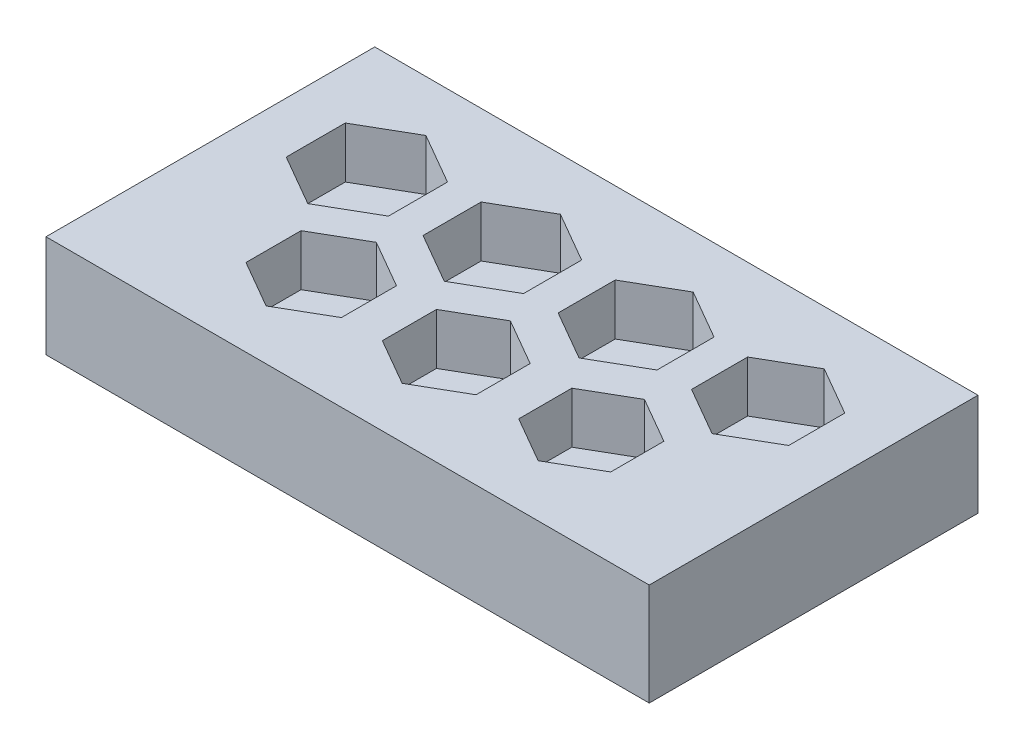
SolidWorks part; units mm, degrees
ref_plane "Front Plane" through (0, 0, 0) normal (0, 0, 1) x (1, 0, 0)
ref_plane "Top Plane" through (0, 0, 0) normal (0, 1, 0) x (1, 0, 0)
ref_plane "Right Plane" through (0, 0, 0) normal (1, 0, 0) x (0, 0, -1)
sketch "Sketch1" plane through (0, 0, 0) normal (0, 1, 0) x (1, 0, 0)
  line L0 (-11.9, 0) -> (-3.95, 0) construction
  line L1 (-8.9, -1.7321) -> (-8.9, 1.7321)
  line L2 (-8.9, 1.7321) -> (-11.9, 3.4641)
  line L3 (-11.9, 3.4641) -> (-14.9, 1.7321)
  line L4 (-14.9, 1.7321) -> (-14.9, -1.7321)
  line L5 (-14.9, -1.7321) -> (-11.9, -3.4641)
  line L6 (-11.9, -3.4641) -> (-8.9, -1.7321)
  line L7 (-1, -1.7032) -> (-1, 1.7032)
  line L8 (-1, 1.7032) -> (-3.95, 3.4064)
  line L9 (-3.95, 3.4064) -> (-6.9, 1.7032)
  line L10 (-6.9, 1.7032) -> (-6.9, -1.7032)
  line L11 (-6.9, -1.7032) -> (-3.95, -3.4064)
  line L12 (-3.95, -3.4064) -> (-1, -1.7032)
  line L13 (6.8, -1.6743) -> (6.8, 1.6743)
  line L14 (6.8, 1.6743) -> (3.9, 3.3486)
  line L15 (3.9, 3.3486) -> (1, 1.6743)
  line L16 (1, 1.6743) -> (1, -1.6743)
  line L17 (1, -1.6743) -> (3.9, -3.3486)
  line L18 (3.9, -3.3486) -> (6.8, -1.6743)
  line L19 (14.5, -1.6454) -> (14.5, 1.6454)
  line L20 (14.5, 1.6454) -> (11.65, 3.2909)
  line L21 (11.65, 3.2909) -> (8.8, 1.6454)
  line L22 (8.8, 1.6454) -> (8.8, -1.6454)
  line L23 (8.8, -1.6454) -> (11.65, -3.2909)
  line L24 (11.65, -3.2909) -> (14.5, -1.6454)
  line L25 (-3.95, 0) -> (0, 0) construction
  line L26 (0, 0) -> (3.9, 0) construction
  line L27 (3.9, 0) -> (11.65, 0) construction
  line L28 (-7.925, -6.654) -> (0, -6.654) construction
  line L29 (-7.925, -3.4208) -> (-10.725, -5.0374)
  line L30 (-10.725, -5.0374) -> (-10.725, -8.2705)
  line L31 (-10.725, -8.2705) -> (-7.925, -9.8871)
  line L32 (-7.925, -9.8871) -> (-5.125, -8.2705)
  line L33 (-5.125, -8.2705) -> (-5.125, -5.0374)
  line L34 (-5.125, -5.0374) -> (-7.925, -3.4208)
  line L35 (7.925, -3.5363) -> (5.225, -5.0951)
  line L36 (5.225, -5.0951) -> (5.225, -8.2128)
  line L37 (5.225, -8.2128) -> (7.925, -9.7717)
  line L38 (7.925, -9.7717) -> (10.625, -8.2128)
  line L39 (10.625, -8.2128) -> (10.625, -5.0951)
  line L40 (10.625, -5.0951) -> (7.925, -3.5363)
  line L41 (0, -3.4785) -> (-2.75, -5.0662)
  line L42 (-2.75, -5.0662) -> (-2.75, -8.2417)
  line L43 (-2.75, -8.2417) -> (0, -9.8294)
  line L44 (0, -9.8294) -> (2.75, -8.2417)
  line L45 (2.75, -8.2417) -> (2.75, -5.0662)
  line L46 (2.75, -5.0662) -> (0, -3.4785)
  line L47 (0, -6.654) -> (7.925, -6.654) construction
  line L48 (0, -6.654) -> (0, 0) construction
  line L49 (-7.925, -6.654) -> (-7.925, 0) construction
  line L51 (-17.9, 6.4641) -> (17.5, 6.4641)
  line L52 (-17.9, 6.4641) -> (-17.9, -12.8294)
  line L53 (-17.9, -12.8294) -> (17.5, -12.8294)
  line L54 (17.5, 6.4641) -> (17.5, -12.8294)
  circle A0 centre (-11.9, 0) radius 3 construction
  circle A1 centre (-3.95, 0) radius 2.95 construction
  circle A2 centre (3.9, 0) radius 2.9 construction
  circle A3 centre (11.65, 0) radius 2.85 construction
  circle A4 centre (-7.925, -6.654) radius 2.8 construction
  circle A5 centre (7.925, -6.654) radius 2.7 construction
  circle A6 centre (0, -6.654) radius 2.75 construction
  dimension "D1" = 6
  dimension "D2" = 5.9
  dimension "D3" = 5.8
  dimension "D4" = 5.7
  dimension "D5" = 5.6
  dimension "D6" = 5.5
  dimension "D7" = 5.4
  dimension "D8" = 2
  dimension "D9" = 1
  dimension "D10" = 2
  dimension "D11" = 2
  dimension "D12" = 2
  dimension "D13" = 3
  dimension "D14" = 3
  dimension "D15" = 3
  dimension "D16" = 3
extrude "Boss-Extrude1" add sketch "Sketch1" along normal blind 3
extrude "Boss-Extrude2" add sketch "Sketch1<2>" against normal blind 3 contours L33 L34 L29 L30 L31 L32 | L5 L6 L1 L2 L3 L4 | L11 L12 L7 L8 L9 L10 | L45 L46 L41 L42 L43 L44 | L39 L40 L35 L36 L37 L38 | L17 L18 L13 L14 L15 L16 | L23 L24 L19 L20 L21 L22 | L54 L51 L52 L53 L46 L45 L44 L43 L42 L41 L40 L39 L38 L37 L36 L35 L34 L33 L32 L31 L30 L29 L24 L23 L22 L21 L20 L19 L18 L17 L16 L15 L14 L13 L12 L11 L10 L9 L8 L7 L6 L5 L4 L3 region at (-11.9, 0, 0) region at (-3.95, 0, 0) region at (3.9, 0, 0) region at (11.65, 0, 0) region at (-7.925, 0, 6.654) region at (7.925, 0, 6.654) region at (0, 0, 6.654) region at (-0.1499, 0, 3.3979)
sketch "Sketch1<2>" plane through (0, 0, 0) normal (0, 1, 0) x (1, 0, 0) same geometry as "Sketch1"
